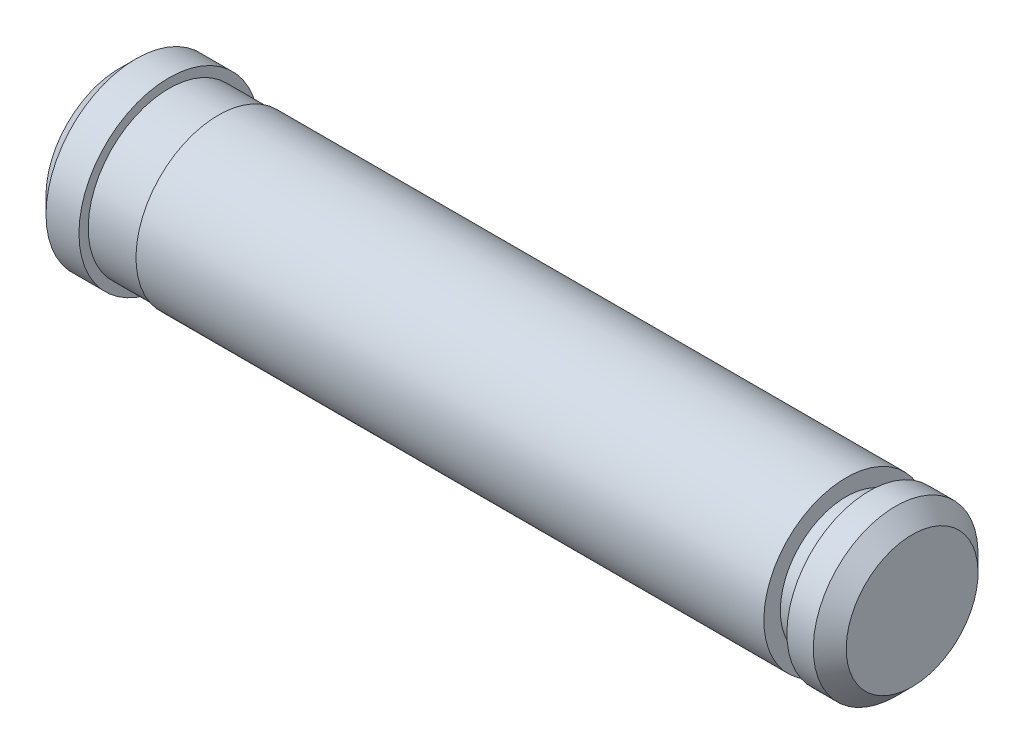
SolidWorks part; units mm, degrees
material "不锈钢 (铁素体)"
ref_plane "前视基准面" through (0, 0, 0) normal (0, 0, 1) x (1, 0, 0)
ref_plane "上视基准面" through (0, 0, 0) normal (0, 1, 0) x (1, 0, 0)
ref_plane "右视基准面" through (0, 0, 0) normal (1, 0, 0) x (0, 0, -1)
ref_plane "基准面4" through (0, 0, 0) normal (0, 0, -1) x (-1, 0, 0)
sketch "草图1" plane through (0, 0, 0) normal (0, 0, -1) x (-1, 0, 0)
  line L0 (-44.8723, 3.1489) -> (-44.8723, 0)
  line L1 (-44.8723, 0) -> (-7, 0)
  line L2 (-7, 0) -> (-7, 3.5128)
  line L3 (-7, 3.5128) -> (-7.7872, 4.3)
  line L4 (-7.7872, 4.3) -> (-9.3617, 4.3)
  line L5 (-9.3617, 4.3) -> (-9.3617, 3.8574)
  line L6 (-9.3617, 3.8574) -> (-11.7234, 3.8574)
  line L7 (-11.7234, 3.8574) -> (-11.7234, 3.9362)
  line L8 (-11.7234, 3.9362) -> (-41.7234, 3.9362)
  line L9 (-41.7234, 3.9362) -> (-41.7234, 3.1489)
  line L10 (-41.7234, 3.1489) -> (-42.8255, 3.1489)
  line L11 (-42.8255, 3.1489) -> (-42.8255, 3.9362)
  line L12 (-42.8255, 3.9362) -> (-44.0851, 3.9362)
  line L13 (-44.0851, 3.9362) -> (-44.8723, 3.1489)
  line L14 (-44.8723, 0) -> (-7, 0) construction
  dimension "D1" = 30
  dimension "D2" = 4.3
revolve "旋转1" add sketch "草图1" angle 360 about L14 reverse direction yes
